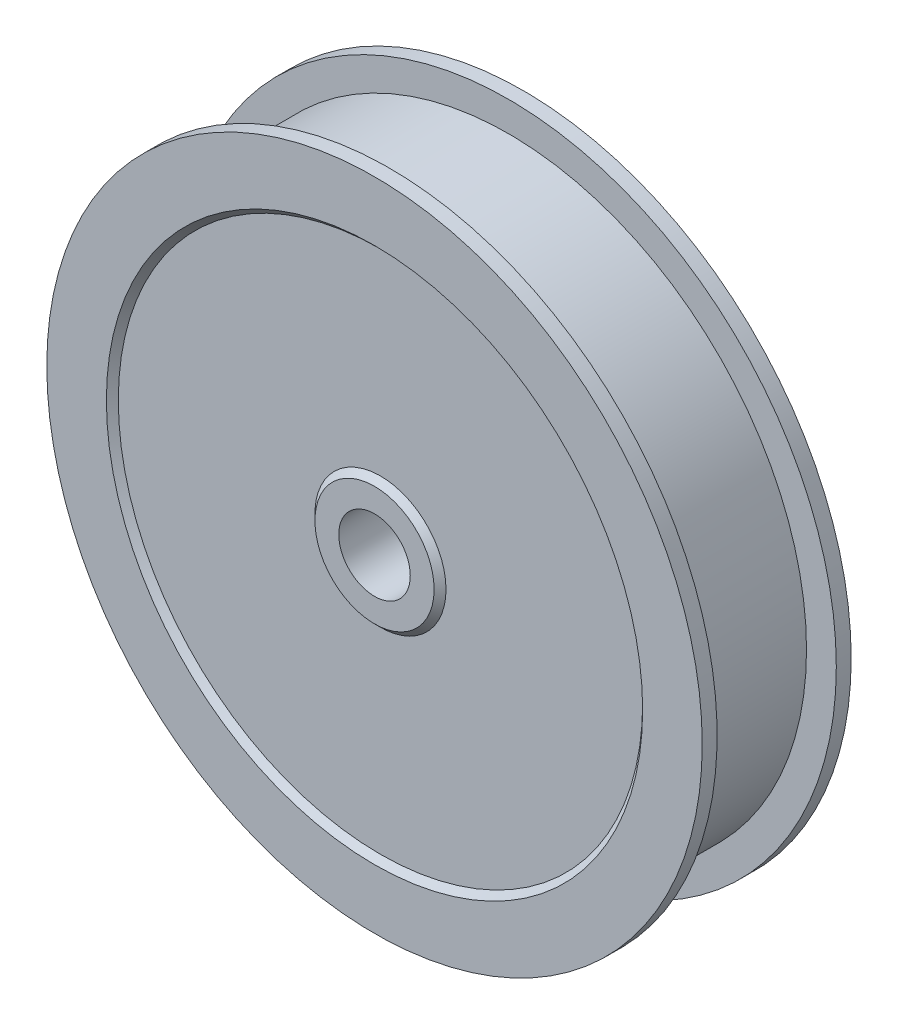
SolidWorks part; units mm, degrees
ref_plane "Alzado" through (0, 0, 0) normal (0, 0, 1) x (1, 0, 0)
ref_plane "Planta" through (0, 0, 0) normal (0, 1, 0) x (1, 0, 0)
ref_plane "Vista lateral" through (0, 0, 0) normal (1, 0, 0) x (0, 0, -1)
sketch "Croquis1" plane through (0, 0, 0) normal (0, 0, 1) x (1, 0, 0)
  circle A0 centre (0, 0) radius 6
  circle A1 centre (0, 0) radius 55
  dimension "D1" = 12
  dimension "D2" = 110
extrude "Saliente-Extruir1" add sketch "Croquis1" along normal blind 25
sketch "Croquis3" plane through (0, 0, 0) normal (1, 0, 0) x (0, 0, -1)
  line L0 (0, 55) -> (-25, 55) construction
  line L1 (-2.5, 50) -> (-22.5, 50)
  line L2 (-2.5, 50) -> (-2.5, 60)
  line L3 (-2.5, 60) -> (-22.5, 60)
  line L4 (-22.5, 50) -> (-22.5, 60)
  line L5 (-2.5, 50) -> (-22.5, 60) construction
  line L6 (-2.5, 60) -> (-22.5, 50) construction
  point P0 (-12.5, 55)
  dimension "D1" = 20
ref_axis "Eje1" through (0, 0, 25) along (0, 0, -1)
revolve "Cortar-Revolución1" cut sketch "Croquis3" angle 360 about axis through (0, 0, 25) along (0, 0, -1)
sketch "Croquis4" plane through (0, 0, 25) normal (0, 0, 1) x (1, 0, 0)
  circle A0 centre (0, 0) radius 10
  circle A1 centre (0, 0) radius 45
extrude "Cortar-Extruir1" cut sketch "Croquis4" against normal blind 1
chamfer "Chaflán1" distance 1 angle 45 2 edges at (45, 0, 24) (10, 0, 24)
ref_plane "Plano1" through (0, 0, 12.5) normal (0, 0, 1) x (1, 0, 0)
mirror "Simetría2" about plane through (0, 0, 12.5) normal (0, 0, 1) of "Chaflán1", "Cortar-Extruir1"
